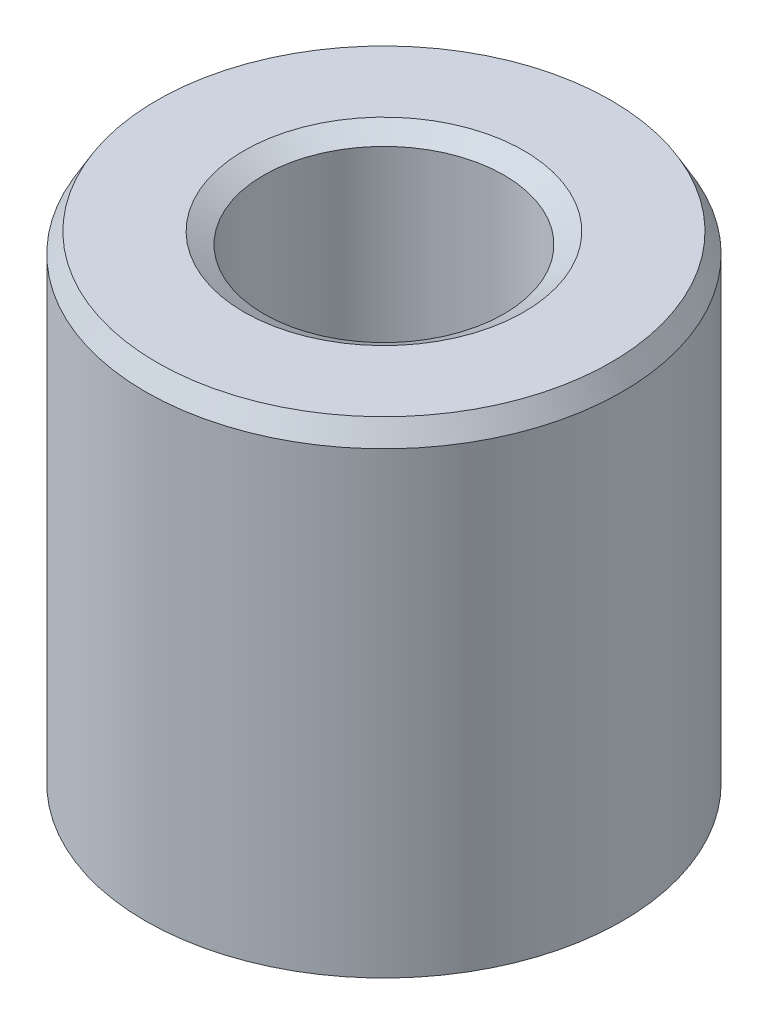
SolidWorks part; units mm, degrees
ref_plane "Front Plane" through (0, 0, 0) normal (0, 0, 1) x (1, 0, 0)
ref_plane "Top Plane" through (0, 0, 0) normal (0, 1, 0) x (1, 0, 0)
ref_plane "Right Plane" through (0, 0, 0) normal (1, 0, 0) x (0, 0, -1)
sketch "Sketch1" plane through (0, 0, 0) normal (0, 1, 0) x (1, 0, 0)
  circle A0 centre (0, 0) radius 22.5
  dimension "SLEEVE_OD" = 45
extrude "Boss-Extrude1" add sketch "Sketch1" along normal blind 46.1854
sketch "Sketch2" plane through (0, 0, 0) normal (0, 1, 0) x (1, 0, 0)
  circle A0 centre (0, 0) radius 11.3412
  dimension "BORE_D" = 22.6825
extrude "Cut-Extrude1" cut sketch "Sketch2" along normal through all
chamfer "Chamfer1" distance 1.8608 angle 30 4 edges at (0, 46.1854, 11.3412) (0, 0, 11.3412) (0, 0, 22.5) (0, 46.1854, 22.5) first distance on face at (0, 46.1854, 11.3412) first distance on face at (0, 0, 11.3412) first distance on face at (0, 46.1854, 22.5)
